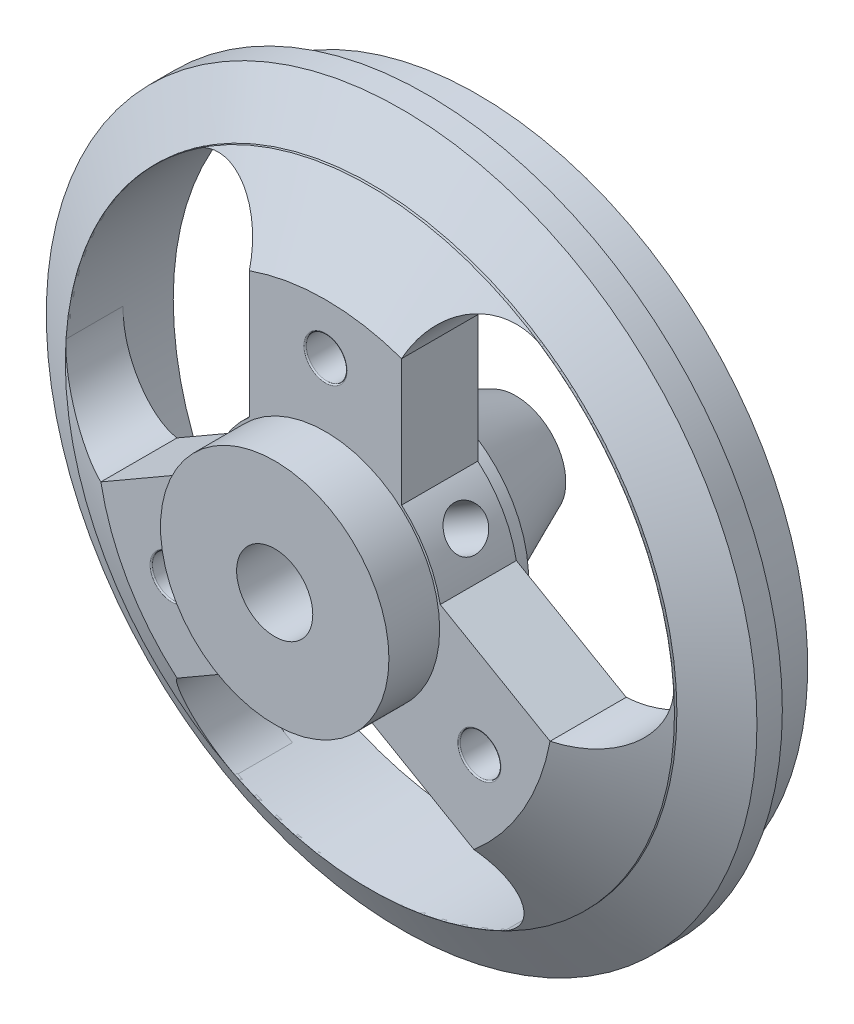
SolidWorks part; units mm, degrees
ref_plane "Front Plane" through (0, 0, 0) normal (0, 0, 1) x (1, 0, 0)
ref_plane "Top Plane" through (0, 0, 0) normal (0, 1, 0) x (1, 0, 0)
ref_plane "Right Plane" through (0, 0, 0) normal (1, 0, 0) x (0, 0, -1)
sketch "Sketch1" plane through (0, 0, 0) normal (0, 0, 1) x (1, 0, 0)
  circle A0 centre (0, 0) radius 14
extrude "Boss-Extrude1" add sketch "Sketch1" along normal blind 4
sketch "Sketch2" plane through (0, 0, 4) normal (0, 0, 1) x (1, 0, 0)
  circle A0 centre (0, 7) radius 1
  circle A1 centre (6.0622, -3.5) radius 1
  circle A2 centre (-6.0622, -3.5) radius 1
  point P8 (0, 0)
extrude "Cut-Extrude2" cut sketch "Sketch2" against normal blind 5
sketch "Sketch4" plane through (0, 0, 4) normal (0, 0, 1) x (1, 0, 0)
  line L0 (-3, 8.4853) -> (-3, 3.4871)
  line L1 (-4.5199, 0.8545) -> (-8.8485, -1.6446)
  line L2 (8.8485, -1.6446) -> (4.5199, 0.8545)
  line L3 (3, 3.4871) -> (3, 8.4853)
  line L4 (-5.8485, -6.8407) -> (-1.5199, -4.3416)
  line L5 (1.5199, -4.3416) -> (5.8485, -6.8407)
  arc A0 (-11.9715, 0.7921) -> (-6.6718, 9.9716) centre (0, 0) cw
  arc A1 (-4.5199, 0.8545) -> (-3, 3.4871) centre (0, 0) cw
  arc A2 (6.6718, 9.9716) -> (11.9715, 0.7921) centre (0, 0) cw
  arc A3 (3, 3.4871) -> (4.5199, 0.8545) centre (0, 0) cw
  arc A4 (6.6718, 9.9716) -> (3, 8.4853) centre (5.4067, 7.8182) ccw
  arc A5 (11.9715, 0.7921) -> (8.8485, -1.6446) centre (9.4742, 0.7732) cw
  arc A6 (-11.9715, 0.7921) -> (-8.8485, -1.6446) centre (-9.4742, 0.7732) ccw
  arc A7 (-6.6718, 9.9716) -> (-3, 8.4853) centre (-5.4067, 7.8182) cw
  arc A8 (5.2998, -10.7637) -> (-5.2998, -10.7637) centre (0, 0) cw
  arc A9 (1.5199, -4.3416) -> (-1.5199, -4.3416) centre (0, 0) cw
  arc A10 (5.2998, -10.7637) -> (5.8485, -6.8407) centre (4.0674, -8.5915) ccw
  arc A11 (-5.2998, -10.7637) -> (-5.8485, -6.8407) centre (-4.0674, -8.5915) cw
  point P28 (0, 0)
extrude "Cut-Extrude4" cut sketch "Sketch4" against normal blind 5
sketch "Sketch6" plane through (0, 0, 4) normal (0, 0, 1) x (1, 0, 0)
  circle A0 centre (0, 0) radius 4.5
extrude "Boss-Extrude2" add sketch "Sketch6" along normal blind 2
sketch "Sketch7" plane through (0, 0, 0) normal (0, 0, -1) x (-1, 0, 0)
  circle A0 centre (0, 0) radius 11.9977
  circle A1 centre (0, 0) radius 13
extrude "Boss-Extrude3" add sketch "Sketch7" along normal blind 2
sketch "Sketch9" plane through (0, 0, 4) normal (0, 0, 1) x (1, 0, 0)
  circle A0 centre (0, 0) radius 12
  circle A1 centre (0, 0) radius 14
extrude "Cut-Extrude8" cut sketch "Sketch9" against normal blind 3
chamfer "Chamfer2" distance 2 angle 30 1 edges at (12, 0, 1) first distance on face at (12, 0, 1)
chamfer "Chamfer6" distance 1.75 distance2 3 1 edges at (12, 0, 4) first distance on face at (12, 0, 2.1547)
sketch "Sketch12" plane through (0, 0, 6) normal (0, 0, 1) x (1, 0, 0)
  circle A0 centre (0, 0) radius 1.5
extrude "Cut-Extrude9" cut sketch "Sketch12" against normal blind 6
sketch "Sketch13" plane through (0, 0, 0) normal (0, 0, -1) x (-1, 0, 0)
  circle A0 centre (0, 0) radius 11.9977
extrude "Cut-Extrude11" cut sketch "Sketch13" against normal blind 1
chamfer "Chamfer7" distance 1 distance2 3 3 edges at (10.3903, -5.9989, 1) (0, 11.9977, 1) (-10.3903, -5.9989, 1) first distance on face at (0, 0, 1.3128)
sketch "Sketch14" plane through (0, 0, 1) normal (0, 0, -1) x (-1, 0, 0)
  circle A0 centre (0, 0) radius 4.5
extrude "Boss-Extrude5" add sketch "Sketch14" along normal blind 0.5
sketch "Sketch15" plane through (0, 0, 0.5) normal (0, 0, -1) x (-1, 0, 0)
  circle A0 centre (0, 0) radius 3.75
extrude "Boss-Extrude7" add sketch "Sketch15" along normal blind 4
chamfer "Chamfer9" distance 4 angle 24 1 edges at (-3.75, 0, -3.5) first distance on face at (-3.75, 0, -3.5)
sketch "Sketch18" plane through (0, 0, -3.5) normal (0, 0, -1) x (-1, 0, 0)
  circle A0 centre (0, 0) radius 1.5
extrude "Cut-Extrude12" cut sketch "Sketch18" against normal blind 7
sketch "Sketch22" plane through (0, 0, 1) normal (0, 0, -1) x (-1, 0, 0)
  circle A0 centre (6.0622, -3.5) radius 1
extrude "Boss-Extrude8" add sketch "Sketch22" along normal blind 0.01 and the other way blind 3
sketch "Sketch23" plane through (0, 0, 1) normal (0, 0, -1) x (-1, 0, 0)
  circle A0 centre (0, 7) radius 1
extrude "Boss-Extrude9" add sketch "Sketch23" along normal blind 0.01 and the other way blind 3
sketch "Sketch24" plane through (0, 0, 1) normal (0, 0, -1) x (-1, 0, 0)
  circle A0 centre (-6.0622, -3.5) radius 1
extrude "Boss-Extrude10" add sketch "Sketch24" along normal blind 0.01 and the other way blind 3
hole_wizard "Tap Drill for M2x0.4 Tap4" positions "Sketch30" profile "Sketch29" hole size "M2x0.4" standard "ANSI Metric"
sketch "Sketch30" plane through (0, 0, 0.99) normal (0, 0, -1) x (-1, 0, 0)
  point P0 (0, 7)
  point P3 (6.0622, -3.5)
  point P6 (-6.0622, -3.5)
sketch "Sketch29" plane through (0, 7, 0.99) normal (1, 0, 0) x (0, 1, 0)
  line L0 (0, 0) -> (0, 10.4807)
  line L1 (0, 10.4807) -> (0.8, 10)
  line L2 (0.8, 10) -> (0.8, 0)
  line L5 (0.8, 0) -> (0, 0)
  line L10 (0, 10.4807) -> (-0.8, 10) construction
  line L11 (0, -6.35) -> (0, 107.95) construction
  dimension "Hole Dia." = 1.6
  dimension "Hole Depth" = 10
  dimension "Drill Angle" = 118
fillet "Fillet1" radius 0.05 6 edges at (0.8, 7, 4) (-5.2622, -3.5, 4) (6.8622, -3.5, 4) (5.2622, -3.5, 0.99) (-0.8, 7, 0.99) (-6.8622, -3.5, 0.99)
hole_wizard "Tap Drill for M2x0.4 Tap6" positions "3DSketch5" profile "Sketch38" hole size "M2x0.4" standard "ANSI Metric"
sketch3d "3DSketch5"
  point P0 (3.9466, 2.3631, 2.402)
sketch "Sketch38" plane through (3.9466, 2.3631, 2.402) normal (0, 0, 1) x (-0.5137, 0.858, 0)
  line L0 (0, 0) -> (0, 4.4807)
  line L1 (0, 4.4807) -> (0.8, 4)
  line L2 (0.8, 4) -> (0.8, 0)
  line L5 (0.8, 0) -> (0, 0)
  line L10 (0, 4.4807) -> (-0.8, 4) construction
  line L11 (0, -6.35) -> (0, 107.95) construction
  dimension "Hole Dia." = 1.6
  dimension "Hole Depth" = 4
  dimension "Drill Angle" = 118
